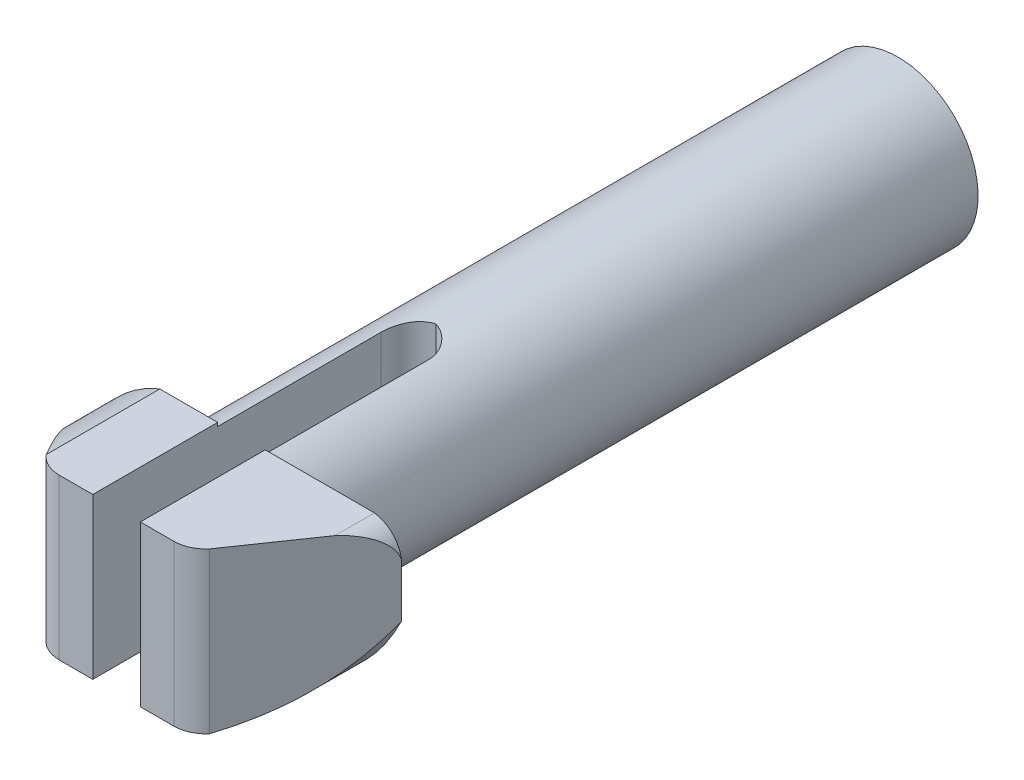
SolidWorks part; units mm, degrees
ref_plane "Front Plane" through (0, 0, 0) normal (0, 0, 1) x (1, 0, 0)
ref_plane "Top Plane" through (0, 0, 0) normal (0, 1, 0) x (1, 0, 0)
ref_plane "Right Plane" through (0, 0, 0) normal (1, 0, 0) x (0, 0, -1)
sketch "Sketch1" plane through (0, 0, 0) normal (0, 1, 0) x (1, 0, 0)
  line L0 (0.5833, 0) -> (5.1317, 0)
  line L4 (-0.3175, 4.953) -> (-3.4925, 4.953)
  line L6 (-0.3175, 4.953) -> (-0.3175, 7.112)
  line L9 (-0.3801, 0.4425) -> (-3.4925, 4.953)
  line L10 (-0.3175, 7.112) -> (6.0325, 7.112)
  line L12 (2.8575, 7.112) -> (2.8575, 0) construction
  line L13 (6.0951, 0.4425) -> (9.2075, 4.953)
  line L14 (6.0325, 4.953) -> (6.0325, 7.112)
  line L15 (6.0325, 4.953) -> (9.2075, 4.953)
  arc A3 (0.5833, 0) -> (-0.3801, 0.4425) centre (0.5833, 1.27) cw
  arc A4 (5.1317, 0) -> (6.0951, 0.4425) centre (5.1317, 1.27) ccw
  point P8 (9.9695, 4.953)
  point P11 (-4.2545, 4.953)
  point P14 (5.715, 0)
  point P17 (0, 0)
  dimension "D1" = 5.715
  dimension "D2" = 14.224
  dimension "D3" = 4.2545
  dimension "D8" = 0.3175
  dimension "D9" = 2.159
extrude "Boss-Extrude1" add sketch "Sketch1" along normal blind 6.35
sketch "Sketch5" plane through (0, 0, 0) normal (0, 0, 1) x (1, 0, 0)
  line L0 (-3.4925, 6.35) -> (-3.4925, 0) construction
  line L1 (9.2075, 6.35) -> (9.2075, 0) construction
  line L2 (-3.4925, 3.175) -> (-3.4925, 6.35)
  line L3 (-3.4925, 6.35) -> (-0.3801, 6.35)
  line L4 (6.0951, 0) -> (9.2075, 0)
  line L5 (6.0951, 0) -> (9.2075, 0) construction
  line L6 (9.2075, 0) -> (9.2075, 3.175)
  line L7 (9.2075, 6.35) -> (9.2075, 5.2705)
  line L8 (9.2075, 6.35) -> (8.128, 6.35)
  line L9 (6.0951, 6.35) -> (9.2075, 6.35) construction
  line L11 (-3.4925, 0) -> (-2.413, 0)
  line L12 (-3.4925, 0) -> (-3.4925, 1.0795)
  arc A0 (9.2075, 5.2705) -> (8.128, 6.35) centre (7.95, 5.0925) ccw
  arc A1 (-3.4925, 1.0795) -> (-2.413, 0) centre (-2.235, 1.2575) ccw
  spline S1 degree 2 poles (-3.4925, 3.175) (-2.286, 5.5951) (-0.3801, 6.35) knots 0 0 0 0.524463 0.524463 0.524463
  spline S2 degree 2 poles (9.2075, 3.175) (8.001, 0.7549) (6.0951, 0) knots 0 0 0 0.524463 0.524463 0.524463
  dimension "D3" = 2.54
  dimension "D6" = 2.54
  dimension "D1" = 1.0795
  dimension "D2" = 1.0795
  dimension "D4" = 1.0795
  dimension "D5" = 1.0795
extrude "Cut-Extrude3" cut sketch "Sketch5" against normal up to surface (4.953 mm away) up to face at (7.62, 3.175, -4.953)
sketch "Sketch7" plane through (0, 0, -7.112) normal (0, 0, -1) x (-1, 0, 0)
  line L1 (-6.0325, 6.35) -> (0.3175, 6.35)
  line L2 (-6.0325, 6.35) -> (-6.0325, 0)
  line L3 (-6.0325, 0) -> (0.3175, 0)
  line L4 (0.3175, 6.35) -> (0.3175, 0)
extrude "Cut-Extrude5" cut sketch "Sketch7" against normal up to surface (2.159 mm away) up to face at (-1.5062, 3.0603, -4.953)
sketch "Sketch9" plane through (0, 0, -4.953) normal (0, 0, -1) x (-1, 0, 0)
  line L0 (-6.0951, 0) -> (0.3801, 6.35) construction
  circle A0 centre (-2.8575, 3.175) radius 3.175
extrude "Boss-Extrude4" add sketch "Sketch9" along normal blind 26.035
sketch "Sketch10" plane through (0, 6.35, 0) normal (0, 1, 0) x (1, 0, 0)
  line L0 (0.5833, 0) -> (5.1317, 0) construction
  line L2 (3.8006, 0) -> (3.8006, 12.7)
  line L3 (3.8006, 12.7) -> (1.9144, 12.7)
  line L4 (1.9144, 0) -> (1.9144, 12.7)
  line L5 (2.8575, 0) -> (1.9144, 12.7) construction
  line L6 (3.8006, 12.7) -> (2.8575, 0) construction
  line L7 (1.9144, 0) -> (3.8006, 0)
  point P0 (2.8575, 0)
  dimension "D1" = 12.7
  dimension "D2" = 0
extrude "Cut-Extrude6" cut sketch "Sketch10" against normal up to surface (6.35 mm away) up to face at (1.9446, 0, -2.3652)
fillet "Fillet1" radius 1.27 2 edges at (1.9144, 3.175, -12.7) (3.8006, 3.175, -12.7)
